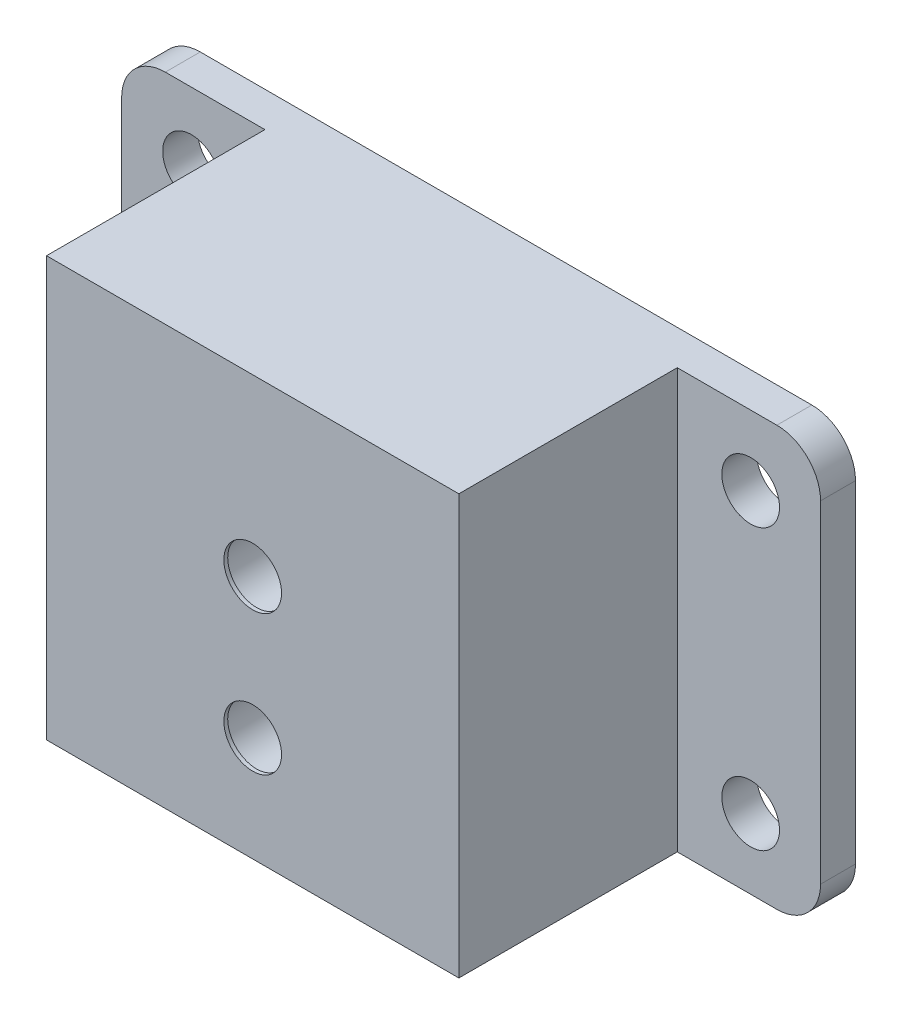
SolidWorks part; units mm, degrees
ref_plane "Front Plane" through (0, 0, 0) normal (1, 0, 0) x (0, 1, 0)
ref_plane "Top Plane" through (0, 0, 0) normal (0, 0, 1) x (0, 1, 0)
ref_plane "Right Plane" through (0, 0, 0) normal (0, 1, 0) x (-1, 0, 0)
sketch "Sketch1" plane through (0, 0, 0) normal (0, 0, 1) x (0, 1, 0)
  line L0 (-24, 12.2) -> (-4, 12.2)
  line L1 (0, 0) -> (-24, 0)
  line L2 (0, 0) -> (0, 40)
  line L3 (0, 40) -> (-24, 40)
  line L4 (-24, 0) -> (-24, 12.2)
  line L5 (-4, 12.2) -> (-4, 27.8)
  line L6 (-4, 27.8) -> (-24, 27.8)
  line L7 (-24, 27.8) -> (-24, 40)
  circle A0 centre (-20, 4) radius 1.65
  circle A1 centre (-4, 4) radius 1.65
  circle A2 centre (-4, 36) radius 1.65
  circle A3 centre (-20, 36) radius 1.65
  dimension "D1" = 3.3
  dimension "D4" = 20
  dimension "D5" = 4
  dimension "D7" = 20
  dimension "D9" = 32
  dimension "D11" = 4
  dimension "D12" = 20
  dimension "D3" = 4
  dimension "D10" = 4
  dimension "D2" = 15.6
  dimension "D6" = 4
extrude "Boss-Extrude1" add sketch "Sketch1" along normal blind 2
sketch "Sketch2" plane through (0, 0, 2) normal (0, 0, 1) x (1, 0, 0)
  line L0 (-27.8, -24) -> (-27.8, -4)
  line L1 (-27.8, -4) -> (-12.2, -4)
  line L2 (-12.2, -4) -> (-12.2, -24)
  line L3 (-12.2, -24) -> (-8.2, -24)
  line L4 (-12.2, -24) -> (0, -24) construction
  line L5 (-8.2, -24) -> (-8.2, 0)
  line L6 (0, 0) -> (-40, 0) construction
  line L7 (-8.2, 0) -> (-31.8, 0)
  line L8 (-31.8, 0) -> (-31.8, -24)
  line L9 (-40, -24) -> (-27.8, -24) construction
  line L10 (-31.8, -24) -> (-27.8, -24)
  dimension "D1" = 4
  dimension "D2" = 4
extrude "Boss-Extrude2" add sketch "Sketch2" along normal blind 7.5
sketch "Sketch3" plane through (0, 0, 9.5) normal (0, 0, 1) x (1, 0, 0)
  line L1 (-31.8, 0) -> (-8.2, 0)
  line L2 (-31.8, 0) -> (-31.8, -24)
  line L3 (-31.8, -24) -> (-8.2, -24)
  line L4 (-8.2, 0) -> (-8.2, -24)
  circle A0 centre (-20, -18) radius 1.65
  circle A1 centre (-20, -10) radius 1.65
  point P8 (-20, 0)
  point P11 (0, 0)
  dimension "D1" = 3.3
  dimension "D3" = 14
  dimension "D2" = 6
extrude "Boss-Extrude3" add sketch "Sketch3" along normal blind 5
fillet "Fillet1" radius 2.5 4 edges at (0, -24, 1) (0, 0, 1) (-40, 0, 1) (-40, -24, 1)
sketch "Sketch5" plane through (0, 0, 9.5) normal (0, 0, -1) x (1, 0, 0)
  circle A0 centre (-20, 18) radius 2
  circle A1 centre (-20, 18) radius 1.65 construction
  circle A2 centre (-20, 10) radius 2
  dimension "D1" = 4
extrude "Cut-Extrude1" cut sketch "Sketch5" against normal blind 4.78
